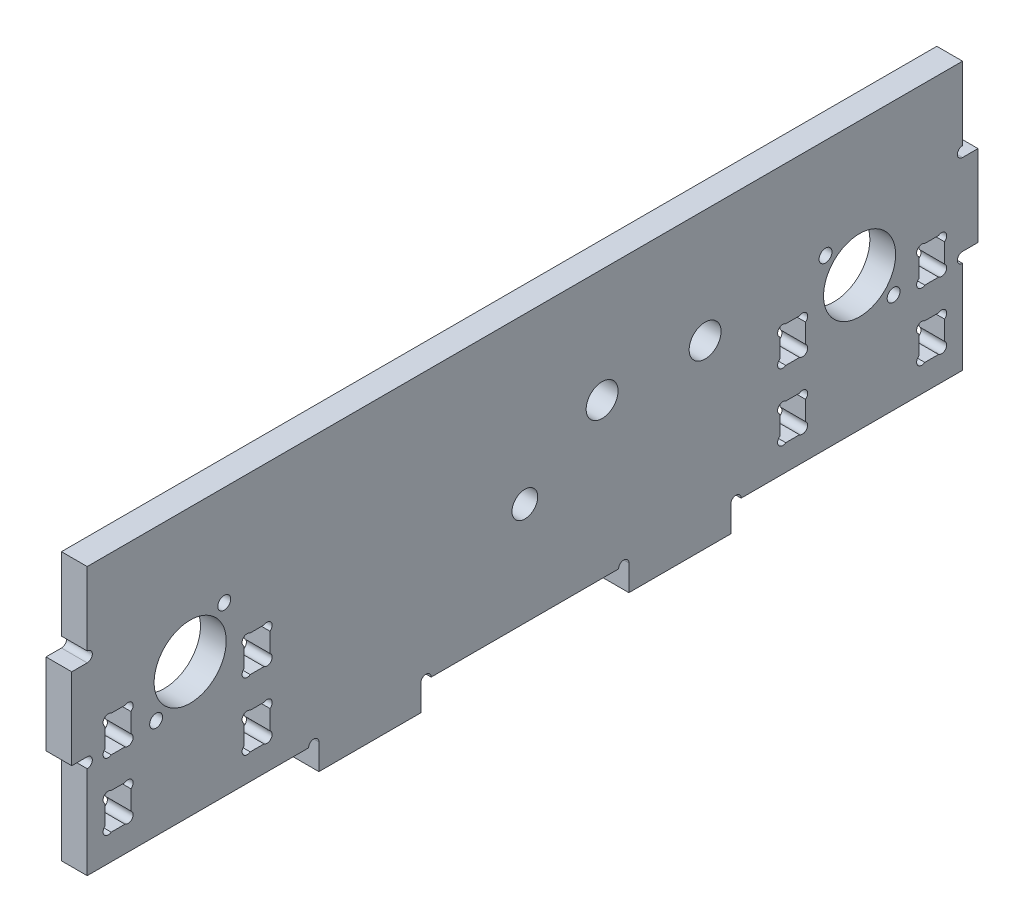
SolidWorks part; units mm, degrees
ref_plane "정면" through (0, 0, 0) normal (0, 0, 1) x (1, 0, 0)
ref_plane "윗면" through (0, 0, 0) normal (0, 1, 0) x (1, 0, 0)
ref_plane "우측면" through (0, 0, 0) normal (1, 0, 0) x (0, 0, -1)
sketch "스케치1" plane through (0, 0, 0) normal (1, 0, 0) x (0, 0, -1)
  line L1 (0, 0) -> (170, 0)
  line L2 (0, 0) -> (0, 52)
  line L3 (0, 52) -> (170, 52)
  line L4 (170, 0) -> (170, 52)
  dimension "D1" = 170
  dimension "D2" = 52
extrude "보스-돌출1" add sketch "스케치1" along normal blind 5
sketch "스케치2" plane through (5, 0, 0) normal (1, 0, 0) x (0, 0, -1)
  line L0 (170, 26) -> (150, 26) construction
  line L1 (170, 0) -> (170, 52) construction
  line L2 (150, 26) -> (20, 26) construction
  line L3 (20, 26) -> (0, 26) construction
  line L4 (0, 52) -> (0, 0) construction
  circle A0 centre (150, 26) radius 7
  circle A1 centre (20, 26) radius 7
  dimension "D2" = 14
  dimension "D1" = 20
extrude "컷-돌출1" cut sketch "스케치2" against normal blind 10
sketch "스케치3" plane through (5, 0, 0) normal (1, 0, 0) x (0, 0, -1)
  line L0 (0, 0) -> (170, 0) construction
  line L1 (45, 0) -> (64.8, 0)
  line L2 (45, 0) -> (45, -5)
  line L3 (45, -5) -> (64.8, -5)
  line L4 (64.8, 0) -> (64.8, -5)
  line L5 (0, -5) -> (44.9, -5) construction
  line L6 (64.8, -5) -> (105.2, -5) construction
  line L7 (125, 0) -> (105.2, 0)
  line L8 (125, 0) -> (125, -5)
  line L9 (125, -5) -> (105.2, -5)
  line L10 (105.2, 0) -> (105.2, -5)
  line L11 (125, -5) -> (170, -5) construction
  line L12 (170, -5) -> (170, 0) construction
  line L13 (0, 0) -> (0, -5) construction
  line L14 (0, 0) -> (0, -5) construction
  line L15 (0, -5) -> (45, -5) construction
  dimension "D1" = 45
  dimension "D2" = 19.8
extrude "보스-돌출2" add sketch "스케치3" against normal blind 5
sketch "스케치6" plane through (5, 0, 0) normal (1, 0, 0) x (0, 0, -1)
  line L0 (151.2, 0) -> (151.2, 6)
  line L1 (148.1, 10) -> (151.2, 10) construction
  line L2 (146.9, 6) -> (146.9, 8.8) construction
  line L3 (151.2, 6) -> (151.2, 8.8) construction
  line L4 (148.1, 0) -> (151.2, 0)
  line L5 (146.9, 8.8) -> (148.1, 8.8)
  line L6 (148.1, 0) -> (148.1, 6)
  line L7 (152.4, 8.8) -> (152.4, 6) construction
  line L8 (148.1, 6) -> (146.9, 6)
  line L9 (148.1, 8.8) -> (148.1, 6) construction
  line L10 (151.2, 8.8) -> (151.2, 10)
  line L11 (148.1, 6) -> (151.2, 6) construction
  line L12 (148.1, 8.8) -> (151.2, 8.8) construction
  line L13 (151.2, 8.8) -> (152.4, 8.8)
  line L14 (148.1, 8.8) -> (148.1, 10)
  line L15 (149.65, 10) -> (149.65, 12.1831) construction
  line L16 (152.4, 6) -> (151.2, 6)
  line L18 (64.8, 0) -> (105.2, 0) construction
  line L19 (101.2, 0) -> (101.2, 6)
  line L20 (98.1, 10) -> (101.2, 10) construction
  line L21 (96.9, 6) -> (96.9, 8.8) construction
  line L22 (101.2, 6) -> (101.2, 8.8) construction
  line L23 (98.1, 0) -> (101.2, 0)
  line L24 (96.9, 8.8) -> (98.1, 8.8)
  line L25 (98.1, 0) -> (98.1, 6)
  line L26 (102.4, 8.8) -> (102.4, 6) construction
  line L27 (98.1, 6) -> (96.9, 6)
  line L28 (98.1, 8.8) -> (98.1, 6) construction
  line L29 (101.2, 8.8) -> (101.2, 10)
  line L30 (98.1, 6) -> (101.2, 6) construction
  line L31 (98.1, 8.8) -> (101.2, 8.8) construction
  line L32 (101.2, 8.8) -> (102.4, 8.8)
  line L33 (98.1, 8.8) -> (98.1, 10)
  line L34 (99.65, 10) -> (99.65, 12.1831) construction
  line L35 (102.4, 6) -> (101.2, 6)
  line L37 (105.2, 0) -> (105.2, -5) construction
  line L71 (85, 52) -> (85, 0) construction
  line L72 (170, 52) -> (0, 52) construction
  line L89 (70.35, 10) -> (70.35, 12.1831) construction
  line L90 (71.9, 8.8) -> (68.8, 8.8) construction
  line L91 (71.9, 6) -> (68.8, 6) construction
  line L92 (71.9, 8.8) -> (71.9, 6) construction
  line L93 (67.6, 8.8) -> (67.6, 6) construction
  line L94 (68.8, 6) -> (68.8, 8.8) construction
  line L95 (73.1, 6) -> (73.1, 8.8) construction
  line L96 (71.9, 10) -> (68.8, 10) construction
  line L97 (20.35, 10) -> (20.35, 12.1831) construction
  line L98 (21.9, 8.8) -> (18.8, 8.8) construction
  line L99 (21.9, 6) -> (18.8, 6) construction
  line L100 (21.9, 8.8) -> (21.9, 6) construction
  line L101 (17.6, 8.8) -> (17.6, 6) construction
  line L102 (18.8, 6) -> (18.8, 8.8) construction
  line L103 (23.1, 6) -> (23.1, 8.8) construction
  line L104 (21.9, 10) -> (18.8, 10) construction
  line L123 (67.6, 6) -> (68.8, 6)
  line L124 (71.9, 8.8) -> (71.9, 10)
  line L125 (68.8, 8.8) -> (67.6, 8.8)
  line L126 (68.8, 8.8) -> (68.8, 10)
  line L127 (71.9, 6) -> (73.1, 6)
  line L128 (71.9, 0) -> (71.9, 6)
  line L129 (73.1, 8.8) -> (71.9, 8.8)
  line L130 (71.9, 0) -> (68.8, 0)
  line L131 (68.8, 0) -> (68.8, 6)
  line L132 (17.6, 6) -> (18.8, 6)
  line L133 (21.9, 8.8) -> (21.9, 10)
  line L134 (18.8, 8.8) -> (17.6, 8.8)
  line L135 (18.8, 8.8) -> (18.8, 10)
  line L136 (21.9, 6) -> (23.1, 6)
  line L137 (21.9, 0) -> (21.9, 6)
  line L138 (23.1, 8.8) -> (21.9, 8.8)
  line L139 (21.9, 0) -> (18.8, 0)
  line L140 (18.8, 0) -> (18.8, 6)
  arc A0 (151.2, 10) -> (148.1, 10) centre (149.65, 10) ccw
  arc A1 (146.9, 8.8) -> (146.9, 6) centre (146.9, 7.4) ccw
  arc A2 (152.4, 6) -> (152.4, 8.8) centre (152.4, 7.4) ccw
  arc A3 (101.2, 10) -> (98.1, 10) centre (99.65, 10) ccw
  arc A4 (96.9, 8.8) -> (96.9, 6) centre (96.9, 7.4) ccw
  arc A5 (102.4, 6) -> (102.4, 8.8) centre (102.4, 7.4) ccw
  arc A18 (67.6, 6) -> (67.6, 8.8) centre (67.6, 7.4) cw
  arc A19 (73.1, 8.8) -> (73.1, 6) centre (73.1, 7.4) cw
  arc A20 (68.8, 10) -> (71.9, 10) centre (70.35, 10) cw
  arc A21 (17.6, 6) -> (17.6, 8.8) centre (17.6, 7.4) cw
  arc A22 (23.1, 8.8) -> (23.1, 6) centre (23.1, 7.4) cw
  arc A23 (18.8, 10) -> (21.9, 10) centre (20.35, 10) cw
  dimension "D1" = 3.1
  dimension "D2" = 4
  dimension "D3" = 5.5
  dimension "D4" = 2.8
  dimension "D7" = 3.1
  dimension "D9" = 5.5
  dimension "D10" = 2.8
  dimension "D12" = 50
extrude "컷-돌출2" [suppressed] cut sketch "스케치6" against normal blind 10
sketch "스케치8" plane through (5, 0, 0) normal (1, 0, 0) x (0, 0, -1)
  line L0 (170, 0) -> (170, 52) construction
  line L1 (170, 35.8) -> (173, 35.8)
  line L2 (170, 35.8) -> (170, 20)
  line L3 (170, 20) -> (173, 20)
  line L4 (173, 35.8) -> (173, 20)
  line L5 (173, 52) -> (173, 35.9) construction
  line L8 (85, 0) -> (85, 52) construction
  line L10 (170, 52) -> (0, 52) construction
  line L11 (-3, 35.8) -> (-3, 20)
  line L12 (0, 20) -> (-3, 20)
  line L13 (0, 35.8) -> (0, 20)
  line L14 (0, 35.8) -> (-3, 35.8)
  line L15 (125, 0) -> (170, 0) construction
  dimension "D1" = 20
  dimension "D2" = 15.8
extrude "보스-돌출3" add sketch "스케치8" against normal blind 5
sketch "스케치7" plane through (5, 0, 0) normal (1, 0, 0) x (0, 0, -1)
  line L0 (64.8, 0) -> (105.2, 0) construction
  line L1 (0, 0) -> (45, 0) construction
  line L2 (64.8, 0) -> (105.2, 0) construction
  line L3 (125, 0) -> (170, 0) construction
  line L4 (170, 35.8) -> (170, 52) construction
  line L5 (170, 0) -> (170, 20) construction
  line L6 (0, 52) -> (0, 35.8) construction
  line L7 (0, 20) -> (0, 0) construction
  circle A0 centre (65.8, 0) radius 1
  circle A1 centre (44, 0) radius 1
  circle A2 centre (104.2, 0) radius 1
  circle A3 centre (126, 0) radius 1
  circle A4 centre (170, 36.8) radius 1
  circle A5 centre (170, 19) radius 1
  circle A6 centre (0, 36.8) radius 1
  circle A7 centre (0, 19) radius 1
  dimension "D1" = 2
extrude "컷-돌출3" cut sketch "스케치7" against normal blind 10
sketch "스케치10" plane through (0, 0, 0) normal (-1, 0, 0) x (0, 0, 1)
  line L0 (-166.5, 25) -> (-161.5, 18) construction
  line L1 (-166.5, 18) -> (-161.5, 18)
  line L2 (-166.5, 18) -> (-166.5, 25)
  line L3 (-166.5, 25) -> (-161.5, 25)
  line L4 (-161.5, 18) -> (-161.5, 25)
  line L5 (-161.5, 25) -> (-166.5, 18) construction
  line L6 (-85, 52) -> (-85, 0) construction
  line L7 (-139.5, 18) -> (-134.5, 18)
  line L8 (-139.5, 18) -> (-139.5, 25)
  line L9 (-139.5, 25) -> (-134.5, 25)
  line L10 (-134.5, 18) -> (-134.5, 25)
  line L11 (-166.5, 5) -> (-161.5, 5)
  line L12 (-166.5, 5) -> (-166.5, 12)
  line L13 (-166.5, 12) -> (-161.5, 12)
  line L14 (-161.5, 5) -> (-161.5, 12)
  line L15 (-139.5, 12) -> (-134.5, 12)
  line L16 (-139.5, 12) -> (-139.5, 5)
  line L17 (-139.5, 5) -> (-134.5, 5)
  line L18 (-134.5, 12) -> (-134.5, 5)
  line L19 (-170, 52) -> (0, 52) construction
  line L21 (-8.5, 25) -> (-3.5, 18) construction
  line L22 (-3.5, 25) -> (-8.5, 18) construction
  line L23 (-35.5, 12) -> (-35.5, 5)
  line L24 (-30.5, 5) -> (-35.5, 5)
  line L25 (-30.5, 12) -> (-30.5, 5)
  line L26 (-30.5, 12) -> (-35.5, 12)
  line L27 (-8.5, 5) -> (-8.5, 12)
  line L28 (-3.5, 12) -> (-8.5, 12)
  line L29 (-3.5, 5) -> (-3.5, 12)
  line L30 (-3.5, 5) -> (-8.5, 5)
  line L31 (-35.5, 18) -> (-35.5, 25)
  line L32 (-30.5, 25) -> (-35.5, 25)
  line L33 (-30.5, 18) -> (-30.5, 25)
  line L34 (-30.5, 18) -> (-35.5, 18)
  line L35 (-8.5, 18) -> (-8.5, 25)
  line L36 (-3.5, 25) -> (-8.5, 25)
  line L37 (-3.5, 18) -> (-3.5, 25)
  line L38 (-3.5, 18) -> (-8.5, 18)
extrude "컷-돌출4" cut sketch "스케치10" against normal blind 10
sketch "스케치11" plane through (5, 0, 0) normal (1, 0, 0) x (0, 0, -1)
  line L0 (85, 52) -> (85, 0) construction
  line L1 (170, 52) -> (0, 52) construction
  line L3 (161.5, 25) -> (166.5, 18) construction
  line L4 (166.5, 25) -> (161.5, 18) construction
  line L5 (139.5, 18) -> (161.5, 18) construction
  line L6 (161.5, 18) -> (161.5, 12) construction
  line L7 (161.5, 12) -> (139.5, 12) construction
  line L8 (139.5, 12) -> (139.5, 18) construction
  line L9 (150.5, 18) -> (150.5, 12) construction
  line L10 (139.5, 15) -> (161.5, 15) construction
  line L11 (134.5, 25) -> (139.5, 18) construction
  line L12 (139.5, 25) -> (134.5, 18) construction
  line L13 (139.5, 5) -> (134.5, 12) construction
  line L14 (134.5, 5) -> (139.5, 12) construction
  line L15 (166.5, 5) -> (161.5, 12) construction
  line L16 (161.5, 5) -> (166.5, 12) construction
  line L17 (8.5, 5) -> (3.5, 12) construction
  line L18 (3.5, 5) -> (8.5, 12) construction
  line L19 (35.5, 5) -> (30.5, 12) construction
  line L20 (30.5, 5) -> (35.5, 12) construction
  line L21 (30.5, 25) -> (35.5, 18) construction
  line L22 (35.5, 25) -> (30.5, 18) construction
  line L23 (30.5, 15) -> (8.5, 15) construction
  line L24 (19.5, 18) -> (19.5, 12) construction
  line L25 (30.5, 12) -> (30.5, 18) construction
  line L26 (8.5, 12) -> (30.5, 12) construction
  line L27 (8.5, 18) -> (8.5, 12) construction
  line L28 (30.5, 18) -> (8.5, 18) construction
  line L29 (3.5, 25) -> (8.5, 18) construction
  line L30 (8.5, 25) -> (3.5, 18) construction
  circle A0 centre (165.9188, 24.1863) radius 1
  circle A1 centre (162.0812, 24.1863) radius 1
  circle A2 centre (165.9188, 18.8137) radius 1
  circle A3 centre (162.0812, 18.8137) radius 1
  circle A4 centre (138.9188, 18.8137) radius 1
  circle A5 centre (135.0812, 18.8137) radius 1
  circle A6 centre (138.9188, 24.1863) radius 1
  circle A7 centre (135.0812, 24.1863) radius 1
  circle A8 centre (135.0812, 5.8137) radius 1
  circle A9 centre (138.9188, 5.8137) radius 1
  circle A10 centre (135.0812, 11.1863) radius 1
  circle A11 centre (138.9188, 11.1863) radius 1
  circle A12 centre (162.0812, 11.1863) radius 1
  circle A13 centre (165.9188, 11.1863) radius 1
  circle A14 centre (162.0812, 5.8137) radius 1
  circle A15 centre (165.9188, 5.8137) radius 1
  circle A16 centre (4.0812, 5.8137) radius 1
  circle A17 centre (7.9188, 5.8137) radius 1
  circle A18 centre (4.0812, 11.1863) radius 1
  circle A19 centre (7.9188, 11.1863) radius 1
  circle A20 centre (31.0812, 11.1863) radius 1
  circle A21 centre (34.9188, 11.1863) radius 1
  circle A22 centre (31.0812, 5.8137) radius 1
  circle A23 centre (34.9188, 5.8137) radius 1
  circle A24 centre (34.9188, 24.1863) radius 1
  circle A25 centre (31.0812, 24.1863) radius 1
  circle A26 centre (34.9188, 18.8137) radius 1
  circle A27 centre (31.0812, 18.8137) radius 1
  circle A28 centre (7.9188, 18.8137) radius 1
  circle A29 centre (4.0812, 18.8137) radius 1
  circle A30 centre (7.9188, 24.1863) radius 1
  circle A31 centre (4.0812, 24.1863) radius 1
  dimension "D1" = 2
extrude "컷-돌출5" cut sketch "스케치11" against normal blind 10
sketch "스케치12" plane through (5, 0, 0) normal (1, 0, 0) x (0, 0, -1)
  line L0 (170, 42) -> (162, 42)
  line L1 (158, 38.9) -> (158, 42) construction
  line L2 (162, 37.7) -> (159.2, 37.7) construction
  line L3 (162, 42) -> (159.2, 42) construction
  line L4 (170, 38.9) -> (170, 42)
  line L5 (159.2, 37.7) -> (159.2, 38.9)
  line L6 (170, 38.9) -> (162, 38.9)
  line L7 (159.2, 43.2) -> (162, 43.2) construction
  line L8 (162, 38.9) -> (162, 37.7)
  line L9 (159.2, 38.9) -> (162, 38.9) construction
  line L10 (159.2, 42) -> (158, 42)
  line L11 (162, 38.9) -> (162, 42) construction
  line L12 (159.2, 38.9) -> (159.2, 42) construction
  line L13 (159.2, 42) -> (159.2, 43.2)
  line L14 (159.2, 38.9) -> (158, 38.9)
  line L15 (158, 40.45) -> (156.45, 40.45) construction
  line L16 (162, 43.2) -> (162, 42)
  line L17 (160.6, 37.7) -> (160.6, 38.9) construction
  line L18 (160.6, 43.2) -> (160.6, 42) construction
  line L19 (159.2, 40.45) -> (158, 40.45) construction
  line L20 (160.6, 43.2) -> (160.6, 44.6) construction
  line L21 (160.6, 37.7) -> (160.6, 36.3) construction
  line L22 (170, 37.8) -> (170, 52) construction
  line L23 (170, 52) -> (0, 52) construction
  line L24 (85, 52) -> (85, 0) construction
  line L26 (9.4, 37.7) -> (9.4, 36.3) construction
  line L27 (9.4, 43.2) -> (9.4, 44.6) construction
  line L28 (10.8, 40.45) -> (12, 40.45) construction
  line L29 (9.4, 43.2) -> (9.4, 42) construction
  line L30 (9.4, 37.7) -> (9.4, 38.9) construction
  line L31 (12, 40.45) -> (13.55, 40.45) construction
  line L32 (10.8, 38.9) -> (10.8, 42) construction
  line L33 (8, 38.9) -> (8, 42) construction
  line L34 (10.8, 38.9) -> (8, 38.9) construction
  line L35 (10.8, 43.2) -> (8, 43.2) construction
  line L36 (8, 42) -> (10.8, 42) construction
  line L37 (8, 37.7) -> (10.8, 37.7) construction
  line L38 (12, 38.9) -> (12, 42) construction
  line L39 (8, 43.2) -> (8, 42)
  line L40 (10.8, 38.9) -> (12, 38.9)
  line L41 (10.8, 42) -> (10.8, 43.2)
  line L42 (10.8, 42) -> (12, 42)
  line L43 (8, 38.9) -> (8, 37.7)
  line L44 (0, 38.9) -> (8, 38.9)
  line L45 (10.8, 37.7) -> (10.8, 38.9)
  line L46 (0, 38.9) -> (0, 42)
  line L47 (0, 42) -> (8, 42)
  arc A0 (158, 42) -> (158, 38.9) centre (158, 40.45) ccw
  arc A1 (159.2, 37.7) -> (162, 37.7) centre (160.6, 37.7) ccw
  arc A2 (162, 43.2) -> (159.2, 43.2) centre (160.6, 43.2) ccw
  arc A3 (8, 43.2) -> (10.8, 43.2) centre (9.4, 43.2) cw
  arc A4 (10.8, 37.7) -> (8, 37.7) centre (9.4, 37.7) cw
  arc A5 (12, 42) -> (12, 38.9) centre (12, 40.45) cw
  dimension "D1" = 3.1
  dimension "D2" = 5.5
  dimension "D3" = 2.8
  dimension "D4" = 1.2
  dimension "D5" = 10
  dimension "D6" = 3.1
  dimension "D7" = 8
extrude "컷-돌출6" [suppressed] cut sketch "스케치12" against normal blind 10
sketch "스케치13" plane through (5, 0, 0) normal (1, 0, 0) x (0, 0, -1)
  line L0 (120, 30) -> (100, 30) construction
  line L1 (127, 0) -> (170, 0) construction
  line L2 (170, 37.8) -> (170, 52) construction
  line L4 (66.8, 0) -> (103.2, 0) construction
  circle A0 centre (100, 30) radius 3.1
  circle A1 centre (120, 30) radius 3.1
  circle A2 centre (85, 20) radius 2.5
  dimension "D1" = 6.2
  dimension "D5" = 20
  dimension "D6" = 5
  dimension "D2" = 20
  dimension "D3" = 30
  dimension "D4" = 50
extrude "컷-돌출7" cut sketch "스케치13" against normal blind 10
sketch "스케치14" plane through (5, 0, 0) normal (1, 0, 0) x (0, 0, -1)
  line L0 (150, 26) -> (155.6569, 20.3431) construction
  line L1 (155.6569, 20.3431) -> (156.6114, 19.3886) construction
  line L2 (150, 26) -> (150, 14.9084) construction
  line L3 (150, 26) -> (155.6569, 31.6569) construction
  line L4 (85, 52) -> (85, 0) construction
  line L5 (170, 52) -> (0, 52) construction
  circle A1 centre (150, 26) radius 8 construction
  circle A2 centre (156.6114, 19.3886) radius 1.25
  circle A3 centre (143.3886, 32.6114) radius 1.25
  circle A4 centre (13.3886, 19.3886) radius 1.25
  circle A5 centre (26.6114, 32.6114) radius 1.25
  dimension "D1" = 2.5
  dimension "D2" = 1.35
  dimension "D3" = 45
extrude "컷-돌출8" cut sketch "스케치14" against normal blind 10
